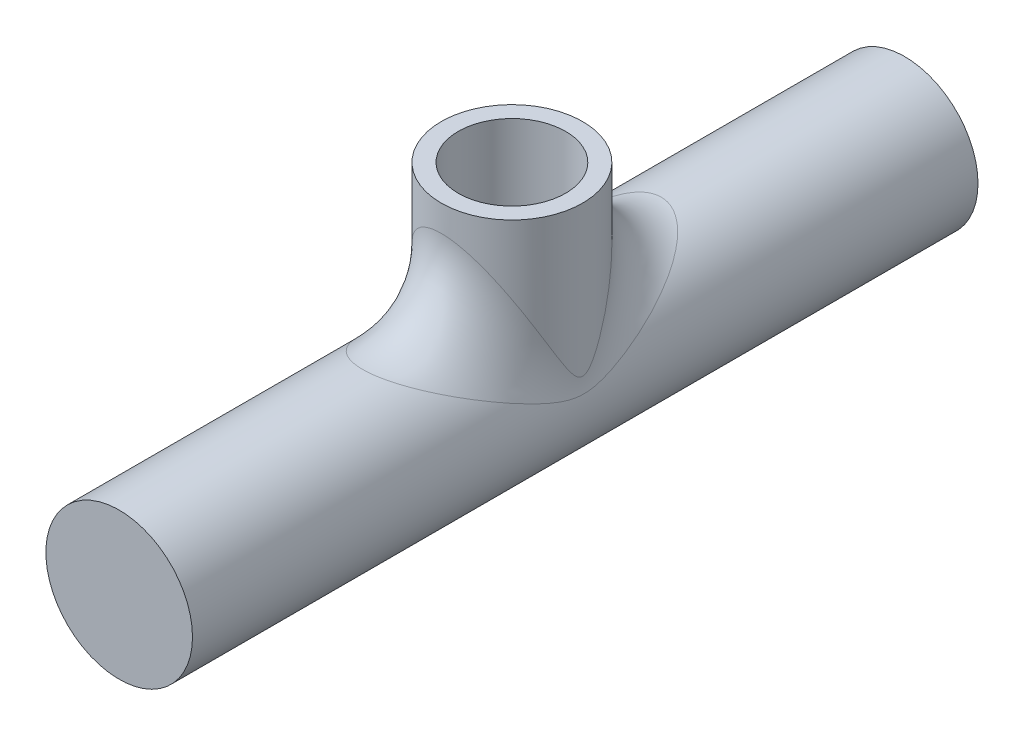
SolidWorks part; units mm, degrees
ref_plane "Front Plane" through (0, 0, 0) normal (0, 0, 1) x (1, 0, 0)
ref_plane "Top Plane" through (0, 0, 0) normal (0, 1, 0) x (1, 0, 0)
ref_plane "Right Plane" through (0, 0, 0) normal (1, 0, 0) x (0, 0, -1)
sketch "Sketch1" plane through (0, 0, 0) normal (0, 0, 1) x (1, 0, 0)
  line L0 (0, 0) -> (0, 14) construction
  circle A0 centre (0, 0) radius 14
  dimension "D1" = 28
extrude "Boss-Extrude1" add sketch "Sketch1" along normal mid plane 150
sketch "Sketch4" plane through (0, 0, -75) normal (0, 0, -1) x (-1, 0, 0)
  line L0 (0, 0) -> (0, 14) construction
  circle A0 centre (0, 0) radius 14 construction
ref_plane "Plane1" through (0, 14, 0) normal (0, 1, 0) x (1, 0, 0)
sketch "Sketch2" plane through (0, 14, 0) normal (0, 1, 0) x (1, 0, 0)
  circle A2 centre (0, 0) radius 13.5
  dimension "D1" = 27
extrude "Boss-Extrude3" add sketch "Sketch2" along normal blind 20 and the other way up to body separate body
fillet "Fillet1" radius 15 1 edges at (1.1285, 13.9544, 13.4528)
sketch "Sketch5" plane through (0, 34, 0) normal (0, 1, 0) x (1, 0, 0)
  circle A0 centre (0, 0) radius 10.25
  dimension "D1" = 20.5
extrude "Cut-Extrude1" cut sketch "Sketch5" against normal blind 35
sketch "Sketch6" plane through (0, -1, 0) normal (0, 1, 0) x (1, 0, 0)
  circle A0 centre (0, 0) radius 10
  dimension "D1" = 20
